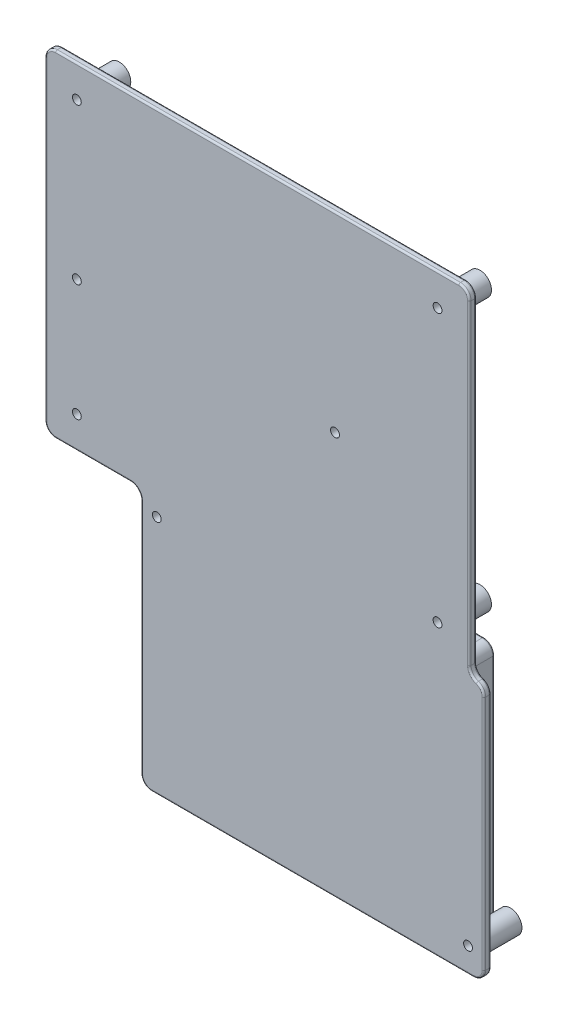
SolidWorks part; units mm, degrees
ref_plane "Front Plane" through (0, 0, 0) normal (0, 0, 1) x (1, 0, 0)
ref_plane "Top Plane" through (0, 0, 0) normal (0, 1, 0) x (1, 0, 0)
ref_plane "Right Plane" through (0, 0, 0) normal (1, 0, 0) x (0, 0, -1)
sketch "Sketch1" plane through (0, 0, 0) normal (0, 0, 1) x (1, 0, 0)
  line L0 (-40.8818, -212.8818) -> (-40.8818, -140)
  line L1 (-45, -45) -> (-165, -45)
  line L2 (-45, -45) -> (-45, -140)
  line L3 (-45, -140) -> (-165, -140)
  line L4 (-165, -45) -> (-165, -140)
  line L5 (-40.8818, -212.8818) -> (-137.8818, -212.8818)
  line L6 (-137.8818, -212.8818) -> (-137.8818, -140)
  line L7 (-50, -50) -> (-160, -50) construction
  line L8 (-50, -50) -> (-50, -45) construction
  line L9 (-50, -50) -> (-45, -50) construction
  line L10 (-160, -135) -> (-165, -135) construction
  line L11 (-160, -135) -> (-160, -140) construction
  line L12 (-137.8818, -141.3758) -> (-137.8818, -148.4172) construction
  line L13 (-47.6022, -212.8818) -> (-124.8824, -212.8818) construction
  line L14 (-40.8818, -140) -> (-45, -140)
  line L15 (-40.8818, -209.3879) -> (-40.8818, -202.3465) construction
  line L16 (-49.8818, -212.8818) -> (-49.8818, -140)
  line L17 (-62.8401, -140) -> (-62.8401, -212.8818)
  line L18 (-49.8818, -208.8824) -> (-49.8818, -141.8812) construction
  line L19 (-62.8401, -150.8685) -> (-62.8401, -170.2192) construction
  line L20 (-128.8818, -212.8818) -> (-128.8818, -140)
  line L21 (-116.1472, -140) -> (-116.1472, -212.8818)
  line L22 (-128.8818, -192.4322) -> (-128.8818, -208.8824) construction
  line L23 (-116.1472, -199.8952) -> (-116.1472, -180.5444) construction
  circle A0 centre (-54, -54) radius 1.25
  circle A1 centre (-156, -54) radius 1.25
  circle A2 centre (-156, -98) radius 1.25
  circle A3 centre (-156, -131) radius 1.25
  circle A4 centre (-54, -131) radius 1.25
  circle A5 centre (-83, -99) radius 1.25
  circle A6 centre (-54, -54) radius 3.25
  circle A7 centre (-156, -54) radius 3.25
  circle A8 centre (-156, -98) radius 3.25
  circle A9 centre (-156, -131) radius 3.25
  circle A10 centre (-54, -131) radius 3.25
  circle A11 centre (-83, -99) radius 3.25
  circle A12 centre (-45.3818, -205.8818) radius 1.25
  circle A13 centre (-133.3818, -144.8818) radius 1.25
  circle A14 centre (-45.3818, -205.8818) radius 3.25
  circle A15 centre (-133.3818, -144.8818) radius 3.25
  dimension "D2" = 2.5
  dimension "D3" = 5
  dimension "D1" = 2
extrude "Boss-Extrude1" add sketch "Sketch1" along normal blind 2 from offset 10 contours L1 L4 L3 L2 A11 A10 A9 A8 A7 A6 | A6 A0 | A7 A1 | A8 A2 | A11 A5 | A9 A3 | A10 A4 | L16 L5 L0 L14 L3 A14 | L3 L17 L5 L16 | L3 L21 L5 L17 | L21 L3 L20 L5 | L5 L20 L3 L6 A15 | A15 A13 | A14 A12 region at (-45.3818, -174.8722, 0) region at (-56.361, -176.4409, 0) region at (-104.9141, -92.4644, 0) region at (-89.4936, -176.4409, 0) region at (-122.5145, -176.4409, 0) region at (-133.3818, -178.1225, 0) region at (-57.1581, -54, 0) region at (-159.1581, -54, 0) region at (-159.1581, -98, 0) region at (-159.1581, -131, 0) region at (-57.1581, -131, 0) region at (-86.1581, -99, 0) region at (-48.5399, -205.8818, 0) region at (-136.5399, -144.8818, 0)
extrude "Boss-Extrude2" add sketch "Sketch1<3>" along normal up to surface (10 mm away) contours A10 A4 | A11 A5 | A6 A0 | A7 A1 | A8 A2 | A9 A3 | A15 A13 | L21 L3 L20 L5 | L3 L17 L5 L16 | A14 A12 region at (-56.361, -176.4409, 0) region at (-122.5145, -176.4409, 0) region at (-57.1581, -54, 0) region at (-159.1581, -54, 0) region at (-159.1581, -98, 0) region at (-159.1581, -131, 0) region at (-57.1581, -131, 0) region at (-86.1581, -99, 0) region at (-48.5399, -205.8818, 0) region at (-136.5399, -144.8818, 0) up to face at (-97.1909, -134.4705, 10)
sketch "Sketch1<3>" plane through (0, 0, 0) normal (0, 0, 1) x (1, 0, 0) same geometry as "Sketch1"
fillet "Fillet1" radius 3 15 edges at (-137.8818, -140, 11) (-45, -45, 11) (-165, -45, 11) (-165, -140, 11) (-128.8818, -140, 5) (-116.1472, -140, 5) (-62.8401, -140, 5) (-49.8818, -140, 5) (-40.8818, -140, 11) (-137.8818, -212.8818, 11) (-128.8818, -212.8818, 5) (-116.1472, -212.8818, 5) (-62.8401, -212.8818, 5) (-49.8818, -212.8818, 5) (-40.8818, -212.8818, 11)
fillet "Fillet2" radius 3 1 edges at (-45, -140, 11)
fillet "Fillet3" radius 0.5 48 edges at (-41.7605, -212.0031, 12) (-40.8818, -176.4409, 12) (-41.4505, -141.2425, 12) (-44.4313, -139.0602, 12) (-45, -92.6514, 12) (-45.8787, -45.8787, 12) (-105, -45, 12) (-164.1213, -45.8787, 12) (-165, -92.5, 12) (-164.1213, -139.1213, 12) (-151.4409, -140, 12) (-138.7605, -140.8787, 12) (-137.8818, -176.4409, 12) (-137.0031, -212.0031, 12) (-117.0258, -212.0031, 0) (-116.1472, -176.4409, 0) (-117.0258, -140.8787, 0) (-122.5145, -140, 0) (-128.0031, -140.8787, 0) (-128.8818, -176.4409, 0) (-128.0031, -212.0031, 0) (-49.8818, -176.4409, 0) (-50.7605, -140.8787, 0) (-56.361, -140, 0) (-61.9614, -140.8787, 0) (-62.8401, -176.4409, 0) (-61.9614, -212.0031, 0) (-56.361, -212.8818, 0) (-130.3818, -212.8818, 10) (-137.0031, -212.0031, 10) (-137.8818, -176.4409, 10) (-138.7605, -140.8787, 10) (-151.4409, -140, 10) (-164.1213, -139.1213, 10) (-165, -92.5, 10) (-164.1213, -45.8787, 10) (-105, -45, 10) (-45.8787, -45.8787, 10) (-48.3818, -212.8818, 10) (-41.7605, -212.0031, 10) (-40.8818, -176.4409, 10) (-41.4505, -141.2425, 10) (-44.4313, -139.0602, 10) (-89.3818, -212.8818, 12) (-122.5145, -212.8818, 0) (-50.7605, -212.0031, 0) (-89.4936, -212.8818, 10) (-45, -92.6514, 10)
